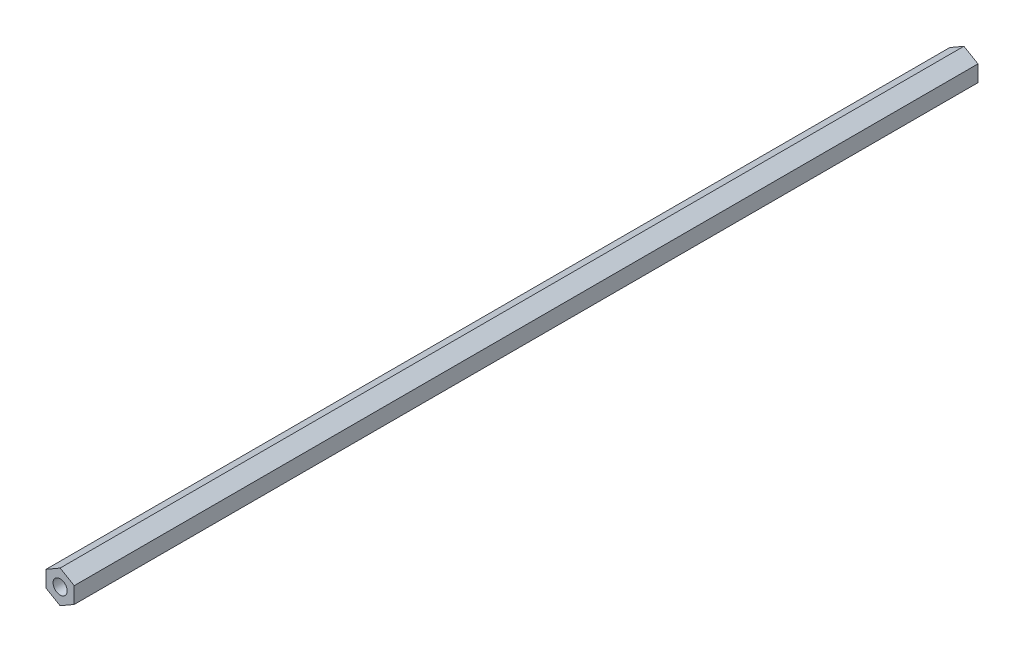
SolidWorks part; units mm, degrees
ref_plane "Front Plane" through (0, 0, 0) normal (0, 0, 1) x (1, 0, 0)
ref_plane "Top Plane" through (0, 0, 0) normal (0, 1, 0) x (1, 0, 0)
ref_plane "Right Plane" through (0, 0, 0) normal (1, 0, 0) x (0, 0, -1)
sketch "Sketch1" plane through (0, 0, 0) normal (0, 0, 1) x (1, 0, 0)
  line L1 (0, 7.3323) -> (-6.35, 3.6662) construction
  line L2 (-6.35, 3.6662) -> (-6.35, -3.6662) construction
  line L3 (-6.35, -3.6662) -> (0, -7.3323) construction
  line L4 (0, -7.3323) -> (6.35, -3.6662) construction
  line L5 (6.35, -3.6662) -> (6.35, 3.6662) construction
  line L6 (6.35, 3.6662) -> (0, 7.3323) construction
  circle A2 centre (0, 0) radius 6.35 construction
  dimension "Width" = 12.7
sketch "Sketch2" plane through (0, 0, 0) normal (1, 0, 0) x (0, 0, -1)
  line L0 (-203.2, 7.3323) -> (203.2, 7.3323) construction
  point P2 (0, 7.3323)
  point P3 (171.45, 7.3323)
  point P4 (-171.45, 7.3323)
  dimension "Length" = 406.4
  dimension "D2" = 31.75
  dimension "D1" = 31.75
sketch "Sketch3" plane through (0, 0, 0) normal (0, 0, 1) x (1, 0, 0)
  line L0 (-6.35, -3.6662) -> (0, -7.3323) construction
  line L1 (0, -7.3323) -> (6.35, -3.6662) construction
  line L2 (6.35, -3.6662) -> (6.35, 3.6662) construction
  line L3 (6.35, 3.6662) -> (0, 7.3323) construction
  line L4 (0, 7.3323) -> (-6.35, 3.6662) construction
  line L5 (-6.35, 3.6662) -> (-6.35, -3.6662) construction
  line L6 (-6.35, -3.6662) -> (0, -7.3323)
  line L7 (0, -7.3323) -> (6.35, -3.6662)
  line L8 (6.35, -3.6662) -> (6.35, 3.6662)
  line L9 (6.35, 3.6662) -> (0, 7.3323)
  line L10 (0, 7.3323) -> (-6.35, 3.6662)
  line L11 (-6.35, 3.6662) -> (-6.35, -3.6662)
extrude "Boss-Extrude2" add sketch "Sketch3" along normal up to vertex (203.2 mm away) and the other way up to vertex (203.2 mm away) up to point (0, 7.3323, 203.2) other way up to point (0, 7.3323, -203.2)
sketch "Sketch4" plane through (0, 0, 203.2) normal (0, 0, 1) x (1, 0, 0)
  point P0 (0, 0)
hole_wizard "1/4 (0.25) Diameter Hole1" positions "Sketch5" profile "Sketch6" hole size "1/4" standard "ANSI Inch"
sketch "Sketch5" plane through (0, 0, 203.2) normal (0, 0, 1) x (1, 0, 0)
  point P0 (0, 0)
sketch "Sketch6" plane through (0, 0, 203.2) normal (1, 0, 0) x (0, -1, 0)
  line L0 (0, 0) -> (0, 27.3077)
  line L1 (0, 27.3077) -> (3.175, 25.4)
  line L2 (3.175, 25.4) -> (3.175, 0)
  line L5 (3.175, 0) -> (0, 0)
  line L10 (0, 27.3077) -> (-3.175, 25.4) construction
  line L11 (0, -6.35) -> (0, 107.95) construction
  dimension "Hole Dia." = 6.35
  dimension "Hole Depth" = 25.4
  dimension "Drill Angle" = 118
equation "\"D2@Sketch2\" = \"D1@Sketch2\""
equation "\"D1@Sketch2\" = \"Width@Sketch1\" * 2.5"
